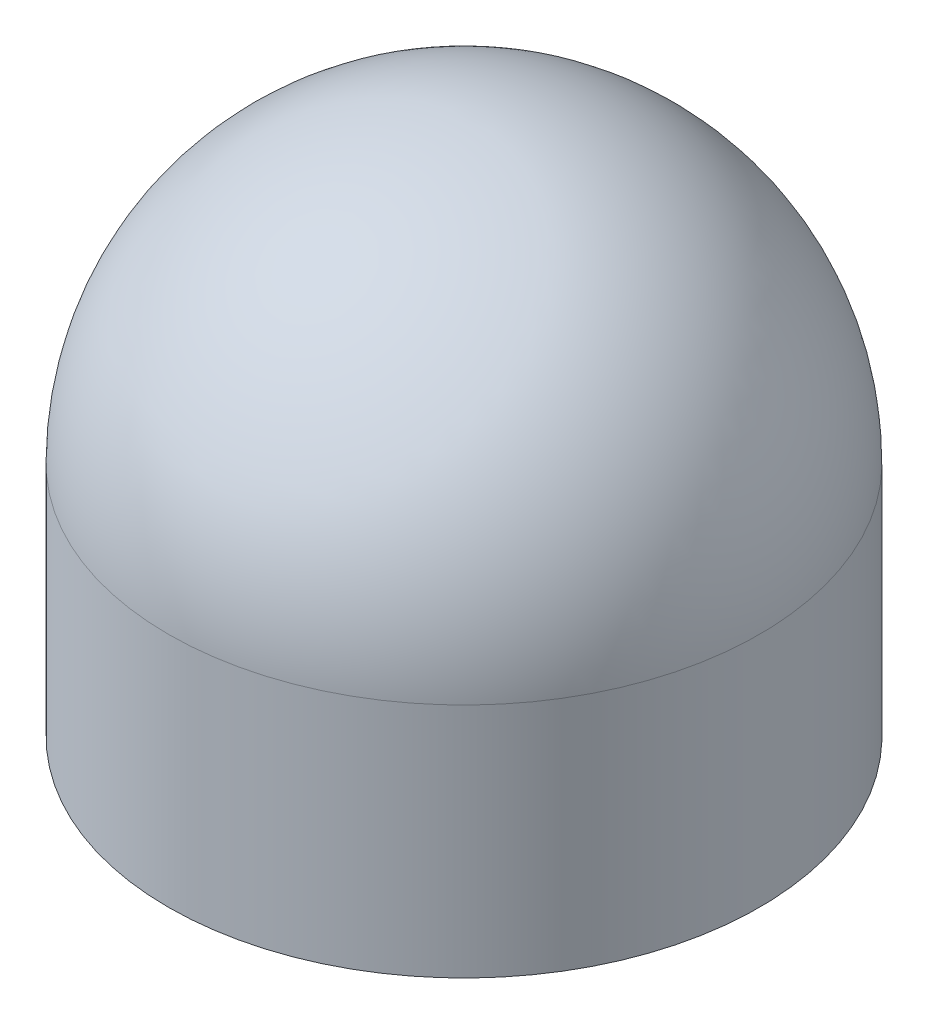
SolidWorks part; units mm, degrees
ref_plane "Front Plane" through (0, 0, 0) normal (0, 0, 1) x (1, 0, 0)
ref_plane "Top Plane" through (0, 0, 0) normal (0, 1, 0) x (1, 0, 0)
ref_plane "Right Plane" through (0, 0, 0) normal (1, 0, 0) x (0, 0, -1)
sketch "Sketch2" plane through (0, 0, 0) normal (0, 1, 0) x (1, 0, 0)
  circle A0 centre (0, 0) radius 7.5
extrude "Boss-Extrude1" add sketch "Sketch2" along normal blind 13.5
sketch "Sketch3" plane through (0, 0, 0) normal (0, -1, 0) x (-1, 0, 0)
  circle A0 centre (0, 0) radius 5
extrude "Cut-Extrude1" cut sketch "Sketch3" against normal blind 5
fillet "Fillet1" radius 7.5 1 edges at (0, 13.5, 7.5)
thread "Thread1" pitch 2 method extrude profile "Thread Profile2" start angle 5, offset 1, length 5, pitch 2, diameter 10
ref_plane "Plane2" through (4.981, -1, -0.4358) normal (0.0872, 0, 0.9962) x (0.9962, 0, -0.0872)
sketch "Thread Profile2" plane through (4.981, -1, -0.4358) normal (0.0872, 0, 0.9962) x (0.9962, 0, -0.0872)
  line L0 (0, 0) -> (0, 2) construction
  line L11 (0, 0) -> (0, 1.75)
  line L12 (0, 1.75) -> (-1.0825, 1.125)
  line L13 (-1.0825, 1.125) -> (-1.0825, 0.625)
  line L15 (-1.0825, 0.625) -> (0, 0)
  line L17 (-1.0825, 0.875) -> (0, 0.875) construction
  point P2 (0, 0)
  dimension "Pitch" = 2
  dimension "Profile_Angle" = 60
  dimension "Profile_Land" = 0.5
  dimension "Profile_Height" = 1.0825
sketch "Sketch10" plane through (0, 0, 0) normal (0, -1, 0) x (-1, 0, 0)
  line L1 (-6.2196, -6.2286) -> (8.6986, -6.2286)
  line L2 (-6.2196, -6.2286) -> (-6.2196, 5.7016)
  line L3 (-6.2196, 5.7016) -> (8.6986, 5.7016)
  line L4 (8.6986, -6.2286) -> (8.6986, 5.7016)
extrude "Cut-Extrude2" cut sketch "Sketch10" along normal blind 5
